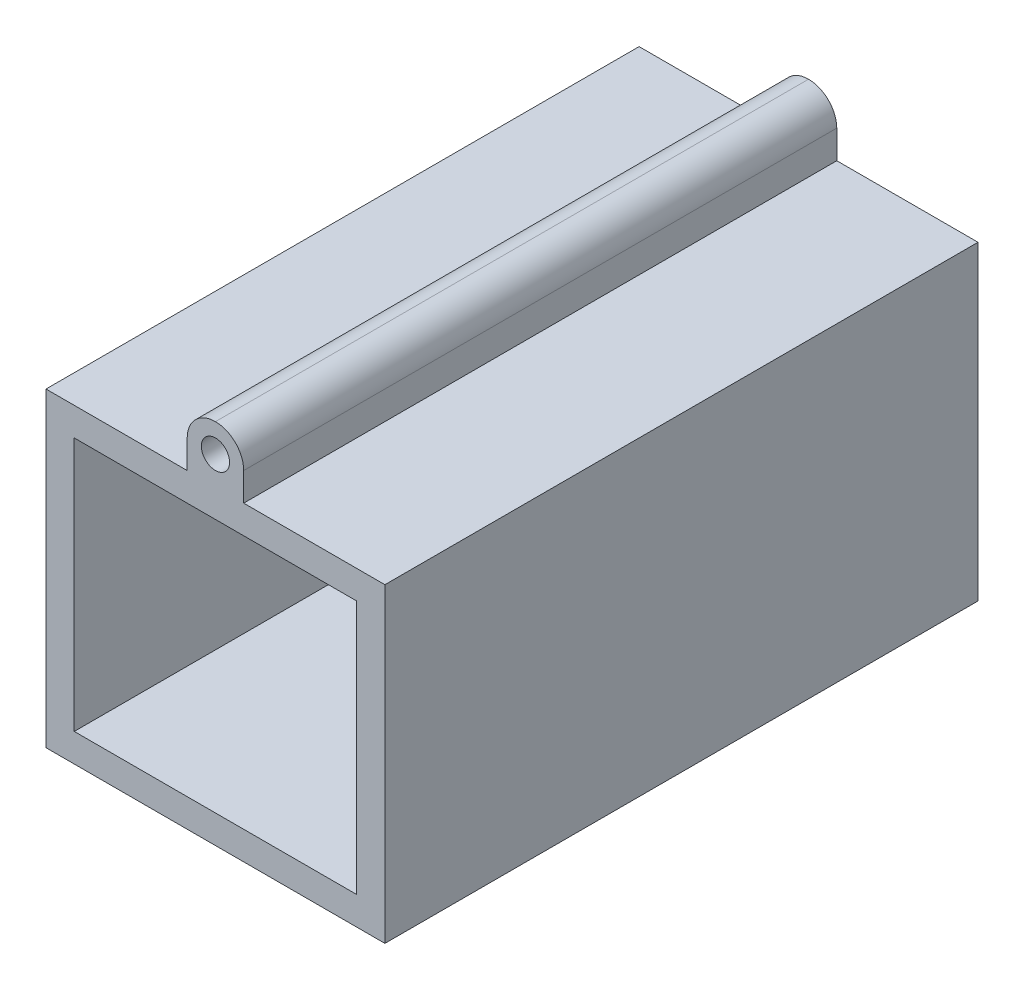
SolidWorks part; units mm, degrees
ref_plane "Front Plane" through (0, 0, 0) normal (0, 0, 1) x (1, 0, 0)
ref_plane "Top Plane" through (0, 0, 0) normal (0, 1, 0) x (1, 0, 0)
ref_plane "Right Plane" through (0, 0, 0) normal (1, 0, 0) x (0, 0, -1)
sketch "Sketch3" plane through (0, 0, 0) normal (0, 0, 1) x (1, 0, 0)
  line L0 (25, -22.5) -> (-25, -22.5)
  line L1 (30, -27.5) -> (-30, -27.5)
  line L2 (30, -27.5) -> (30, 27.5)
  line L3 (30, 27.5) -> (-30, 27.5)
  line L4 (-30, -27.5) -> (-30, 27.5)
  line L5 (30, -27.5) -> (-30, 27.5) construction
  line L6 (30, 27.5) -> (-30, -27.5) construction
  line L7 (-25, -22.5) -> (-25, 22.5)
  line L8 (25, 22.5) -> (-25, 22.5)
  line L9 (25, -22.5) -> (25, 22.5)
  point P0 (0, 0)
  dimension "D1" = 55
  dimension "D2" = 60
  dimension "D3" = 5
extrude "Boss-Extrude1" add sketch "Sketch3" against normal blind 105
sketch "Sketch6" plane through (0, -22.5, 0) normal (0, 1, 0) x (1, 0, 0)
  line L0 (25, 105) -> (25, 0) construction
  line L1 (-25, 105) -> (25, 105)
  line L2 (-25, 105) -> (-25, 100)
  line L3 (-25, 100) -> (25, 100)
  line L4 (25, 105) -> (25, 100)
  dimension "D1" = 5
extrude "Boss-Extrude3" add sketch "Sketch6" along normal blind 10
sketch "Sketch7" plane through (0, 27.5, 0) normal (0, 1, 0) x (1, 0, 0)
  line L1 (5, 0) -> (-5, 0)
  line L2 (5, 0) -> (5, 105)
  line L3 (5, 105) -> (-5, 105)
  line L4 (-5, 0) -> (-5, 105)
  line L5 (5, 0) -> (-5, 105) construction
  line L6 (5, 105) -> (-5, 0) construction
  line L8 (30, 0) -> (-30, 0) construction
  line L9 (30, 105) -> (-30, 105) construction
  point P0 (0, 52.5)
  point P9 (0, 0)
  dimension "D2" = 10
extrude "Boss-Extrude4" add sketch "Sketch7" along normal blind 10
fillet "Fillet1" radius 5 2 edges at (5, 37.5, -52.5) (-5, 37.5, -52.5)
sketch "Sketch8" plane through (0, 0, 0) normal (0, 0, 1) x (1, 0, 0)
  circle A0 centre (0, 32.5) radius 2.5
  dimension "D1" = 5
extrude "Cut-Extrude1" cut sketch "Sketch8" against normal through all
